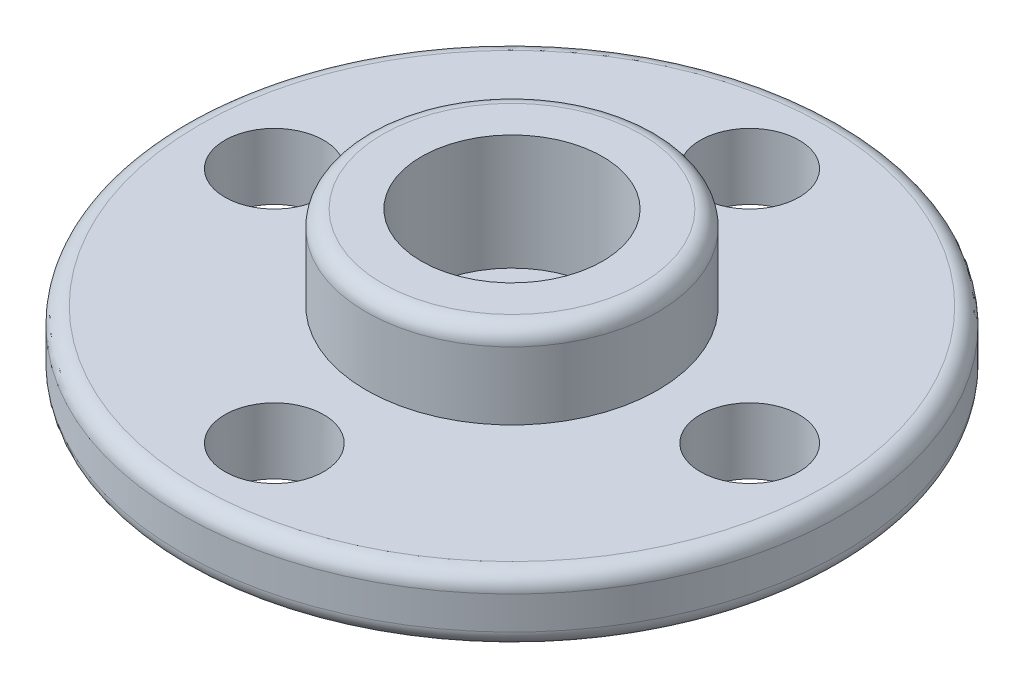
SolidWorks part; units mm, degrees
ref_plane "Front" through (0, 0, 0) normal (0, 0, 1) x (1, 0, 0)
ref_plane "Top" through (0, 0, 0) normal (0, 1, 0) x (1, 0, 0)
ref_plane "Right" through (0, 0, 0) normal (1, 0, 0) x (0, 0, -1)
sketch "Sketch1" plane through (0, 0, 0) normal (0, 1, 0) x (1, 0, 0)
  circle A0 centre (0, 0) radius 10
  circle A1 centre (0, 0) radius 4.425
  dimension "D1" = 20
  dimension "D2" = 8.85
extrude "Boss-Extrude1" add sketch "Sketch1" along normal blind 2
extrude "Boss-Extrude2" add sketch "Sketch1<2>" along normal blind 4.55 contours A1 region at (0, 0, 0)
sketch "Sketch1<2>" plane through (0, 0, 0) normal (0, 1, 0) x (1, 0, 0) same geometry as "Sketch1"
sketch "Sketch2" plane through (0, 4.55, 0) normal (0, 1, 0) x (1, 0, 0)
  circle A0 centre (0, 0) radius 1.5
  circle A1 centre (0, 0) radius 2.75
  dimension "D1" = 5.5
  dimension "D2" = 3
extrude "Cut-Extrude1" cut sketch "Sketch2" against normal blind 3.5 contours A1 A0 | A0 region at (0, 4.55, 0) region at (-2.6722, 4.55, 0)
extrude "Cut-Extrude2" cut sketch "Sketch2<3>" against normal through all both and the other way through all contours A0 region at (0, 4.55, 0)
sketch "Sketch2<3>" plane through (0, 4.55, 0) normal (0, 1, 0) x (1, 0, 0) same geometry as "Sketch2"
sketch "Sketch3" plane through (0, 2, 0) normal (0, 1, 0) x (1, 0, 0)
  line L0 (0, 10) -> (0, 7.2125) construction
  line L1 (0, 7.2125) -> (0, 4.425) construction
  circle A0 centre (0, 7.2125) radius 1.5
  circle A1 centre (0, 0) radius 10 construction
  circle A2 centre (0, 0) radius 4.425 construction
  dimension "D1" = 3
extrude "Cut-Extrude3" cut sketch "Sketch3" against normal through all both and the other way through all
pattern_circular "CirPattern1" count 4 over 360 about axis through (0, 4.55, 0) along (0, -1, 0) of "Cut-Extrude3" reverse direction yes
fillet "Fillet1" radius 0.5 3 edges at (0, 4.55, 4.425) (0, 2, 10) (0, 0, 10)
